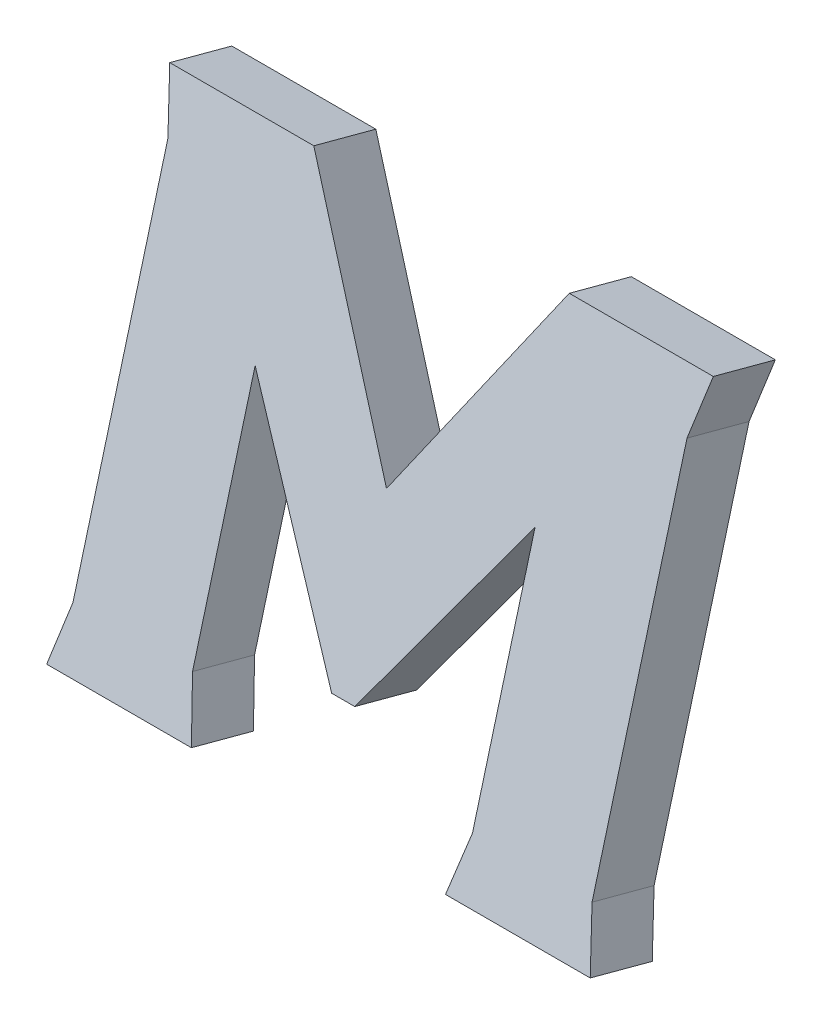
SolidWorks part; units mm, degrees
ref_plane "Front Plane" through (0, 0, 0) normal (0, 0, 1) x (1, 0, 0)
ref_plane "Top Plane" through (0, 0, 0) normal (0, 1, 0) x (1, 0, 0)
ref_plane "Right Plane" through (0, 0, 0) normal (1, 0, 0) x (0, 0, -1)
ref_axis "Axis1" through (-88.99, 0, 0) along (1, 0, 0)
ref_plane "Plane1" through (0, 0, 0) normal (0, 0.2588, 0.9659) x (1, 0, 0)
sketch "Sketch8" plane through (0, 0, 0) normal (0, 0.2588, 0.9659) x (1, 0, 0)
  line L0 (5.7129, 25.3906) -> (0, 0)
  line L1 (0, 0) -> (67.6059, -0.0004)
  line L2 (67.6059, -0.0004) -> (61.5724, 25.3902)
  line L3 (61.5724, 25.3902) -> (61.5719, 138.3796)
  line L4 (61.5719, 138.3796) -> (121.5579, 44.7516)
  line L5 (121.5579, 44.7516) -> (132.3509, 44.7516)
  line L6 (132.3509, 44.7516) -> (192.3324, 138.3796)
  line L7 (192.3324, 138.3796) -> (192.3324, 25.3906)
  line L8 (192.3324, 25.3906) -> (186.303, 0)
  line L9 (186.303, 0) -> (253.9058, -0.0004)
  line L10 (253.9058, -0.0004) -> (248.1933, 25.3902)
  line L11 (248.1933, 25.3902) -> (248.1933, 196.7776)
  line L12 (248.1933, 196.7776) -> (253.9058, 222.1678)
  line L13 (253.9058, 222.1678) -> (186.6194, 222.1676)
  line L14 (186.6194, 222.1676) -> (126.9543, 122.8285)
  line L15 (126.9543, 122.8285) -> (67.285, 222.1676)
  line L16 (67.285, 222.1676) -> (-0.0001, 222.1676)
  line L17 (-0.0001, 222.1676) -> (5.7128, 196.7774)
  line L18 (5.7128, 196.7774) -> (5.7129, 25.3906)
  point P0 (0, 0)
extrude "Boss-Extrude1" add sketch "Sketch8" along normal blind 30
